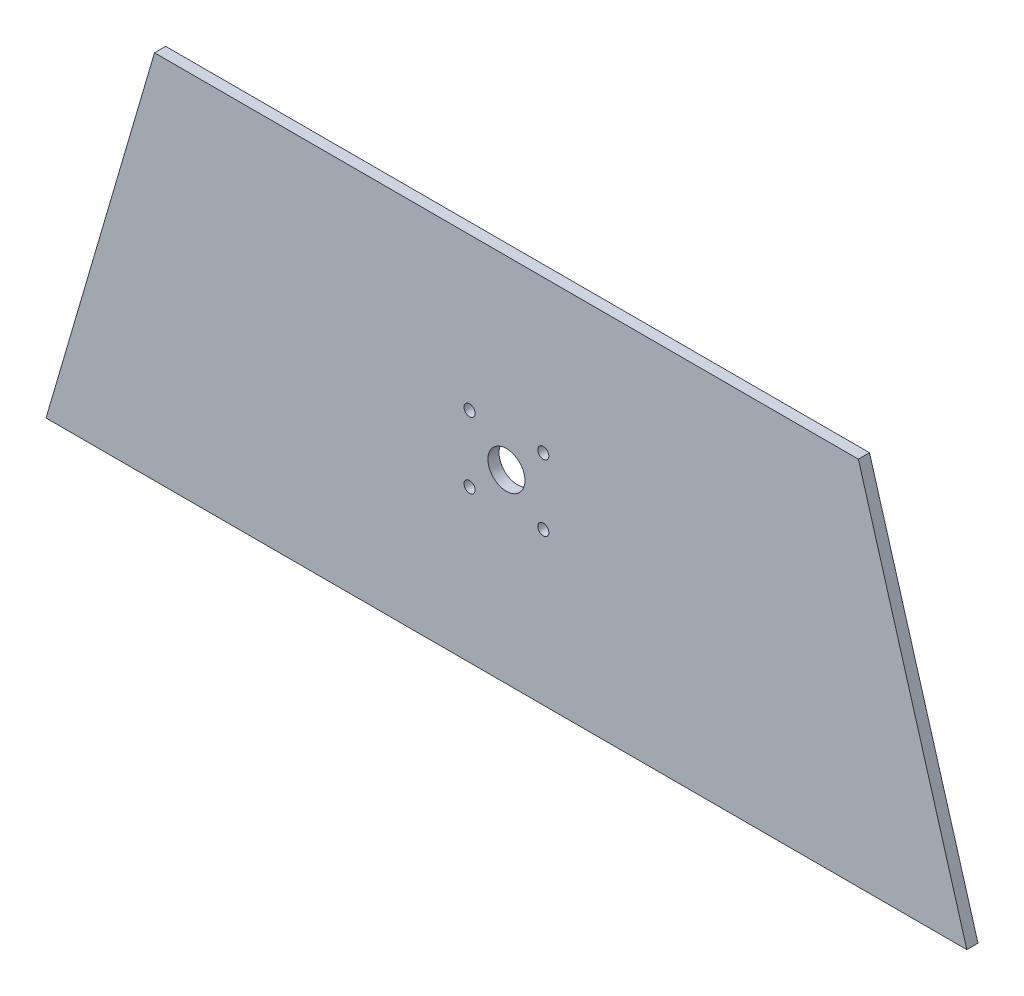
SolidWorks part; units mm, degrees
ref_plane "Front Plane" through (0, 0, 0) normal (0, 0, 1) x (1, 0, 0)
ref_plane "Top Plane" through (0, 0, 0) normal (0, 1, 0) x (1, 0, 0)
ref_plane "Right Plane" through (0, 0, 0) normal (1, 0, 0) x (0, 0, -1)
sketch "Sketch1" plane through (0, 0, 0) normal (0, 0, 1) x (1, 0, 0)
  line L0 (-3.5, 0) -> (245, 0)
  line L3 (149.129, 0) -> (149.129, 100) construction
  line L5 (-3.5, 0) -> (25.7799, 100)
  line L6 (245, 0) -> (215.7201, 100)
  line L7 (25.7799, 100) -> (215.7201, 100)
extrude "Boss-Extrude1" add sketch "Sketch1" along normal blind 3 and the other way blind 0.0067
hole_wizard "Ø10.0mm Dowel Hole1" positions "Sketch2" profile "Sketch3" hole size "Ø10.0" standard "ANSI Metric" end condition up to next
sketch "Sketch2" plane through (0, 0, 3) normal (0, 0, 1) x (1, 0, 0)
  point P0 (120.75, 50)
  point P5 (0, 0)
sketch "Sketch3" plane through (120.75, 50, 3) normal (1, 0, 0) x (0, -1, 0)
  line L0 (0, 0) -> (0, 3.0067)
  line L1 (0, 3.0067) -> (5, 3.0067)
  line L2 (5, 3.0067) -> (5, 0)
  line L5 (5, 0) -> (0, 0)
  line L11 (0, -6.35) -> (0, 107.95) construction
  dimension "Thru Hole Dia." = 10
  dimension "Thru Hole Depth" = 3.0067
hole_wizard "Ø3.0mm Dowel Hole1" positions "Sketch4" profile "Sketch5" hole size "Ø3.0" standard "ANSI Metric" end condition up to next
sketch "Sketch4" plane through (0, 0, 3) normal (0, 0, 1) x (1, 0, 0)
  point P0 (110.8, 58.95)
  point P3 (130.7, 58.95)
  point P6 (130.7, 41.05)
  point P9 (110.8, 41.05)
  point P13 (0, 0)
  point P14 (0, 0)
  point P15 (0, 0)
  point P16 (0, 0)
sketch "Sketch5" plane through (110.8, 58.95, 3) normal (1, 0, 0) x (0, -1, 0)
  line L0 (0, 0) -> (0, 3.0067)
  line L1 (0, 3.0067) -> (1.5, 3.0067)
  line L2 (1.5, 3.0067) -> (1.5, 0)
  line L5 (1.5, 0) -> (0, 0)
  line L11 (0, -6.35) -> (0, 107.95) construction
  dimension "Thru Hole Dia." = 3
  dimension "Thru Hole Depth" = 3.0067
